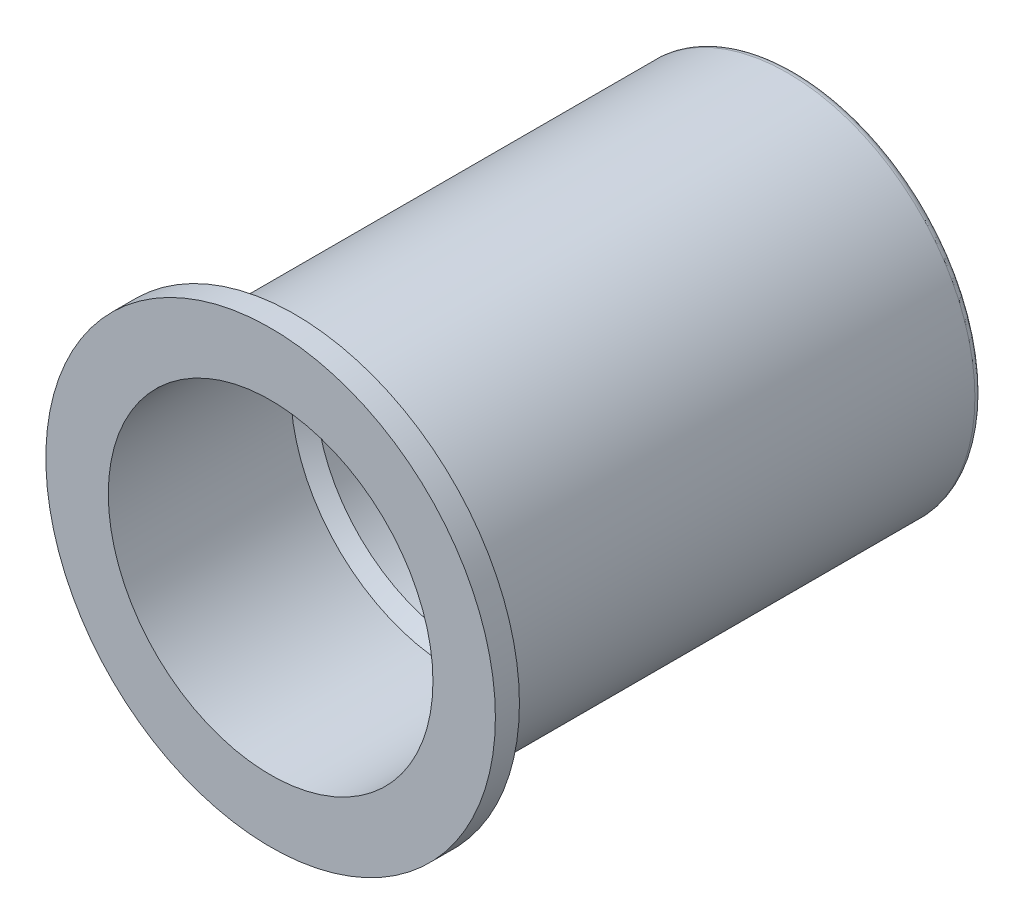
SolidWorks part; units mm, degrees
ref_plane "Front" through (0, 0, 0) normal (0, 0, 1) x (1, 0, 0)
ref_plane "Top" through (0, 0, 0) normal (0, 1, 0) x (1, 0, 0)
ref_plane "Right" through (0, 0, 0) normal (1, 0, 0) x (0, 0, -1)
sketch "Sketch3" plane through (0, 0, 0) normal (0, 0, 1) x (1, 0, 0)
  circle A0 centre (0, 0) radius 9
  dimension "dk" = 18
extrude "BaseHead" add sketch "Sketch3" against normal blind 1.8
sketch "Sketch4" plane through (-3.067, 2.6488, 0) normal (0, 0, -1) x (-1, 0, 0)
  circle A0 centre (-3.067, -2.6488) radius 7.5
  circle A1 centre (-3.067, -2.6488) radius 9 construction
extrude "BaseBody" add sketch "Sketch4" along normal blind 21
sketch "Sketch8" plane through (9, 0, 1.1855) normal (0, 1, 0) x (-1, 0, 0)
  line L0 (9, 2.3542) -> (9, -3.5397) construction
  line L2 (18, -2.1483) -> (16.55, -2.9855)
  line L5 (16.55, -2.9855) -> (18, -2.9855)
  line L7 (18, -2.9855) -> (18, -2.1483)
  dimension "D1" = 30
  dimension "D2" = 15.1
revolve "BearingFace" cut sketch "Sketch8" angle 360 about L0
sketch "Sketch5" plane through (1.6426, -1.4193, 0) normal (0, 0, 1) x (1, 0, 0)
  circle A0 centre (-1.6426, 1.4193) radius 6.5
  circle A2 centre (-1.6426, 1.4193) radius 7.5 construction
extrude "Hole1" cut sketch "Sketch5" against normal blind 7.3
sketch "Sketch6" plane through (-0.0097, -0.1511, -7.3) normal (0, 0, 1) x (1, 0, 0)
  circle A0 centre (0.0097, 0.1511) radius 6
  circle A1 centre (0.0097, 0.1511) radius 6.5 construction
  dimension "D1" = 12
extrude "Hole2" cut sketch "Sketch6" against normal through all
cosmetic thread "ThreadCosmetic1" [suppressed] parameters "D2"=13
fillet "Fillet1" radius 0.3 2 edges at (-7.5, 0, -21) (7.55, 0, -1.8)
chamfer "Chamfer1" distance 0.5 angle 45 1 edges at (6, 0, -7.3)
chamfer "Chamfer2" distance 0.48 angle 45 1 edges at (6, 0, -21)
sketch "Sketch9" plane through (0, 0, 0) normal (0, 1, 0) x (1, 0, 0)
  line L0 (0, 25.2227) -> (0, -4.8181) construction
  line L1 (5.5, 20.77) -> (5.5, 20.27)
  line L2 (5.5, 20.27) -> (6, 20.27)
  line L3 (6, 20.27) -> (6.433, 20.52)
  line L4 (6.433, 20.52) -> (6, 20.77)
  line L5 (6, 20.77) -> (5.5, 20.77)
  line L6 (-6, 20.52) -> (6, 20.52) construction
  dimension "D1" = 12
revolve "Cut-Revolve10" [suppressed] cut sketch "Sketch9" angle 360 about L0
pattern_linear "LPattern10" [suppressed] count 22 spacing 0.6 along (0, 0, 1) of bodies 107
equation "\"D2@Sketch8\"=\"d@Sketch4\"+ 0.1"
equation "\"D1@Chamfer1\" =  ( \"d1@Sketch5\" - \"D1@Sketch6\" )  / 2"
equation "\"D1@Chamfer2\" = \"D1@Sketch6\" / 25"
equation "\"D2@Sketch9\" = (  \"D2@ThreadCosmetic1\" - \"D1@Sketch6\" )  / 2"
equation "\"D1@Sketch9\" = \"D1@Sketch6\""
equation "\"D1@LPattern10\" = ( \"l@BaseBody\" -  \"l1@Hole1\" )  / \"D3@LPattern10\" - 1"
equation "\"D3@LPattern10\" = \"D2@Sketch9\" * 1.2"
